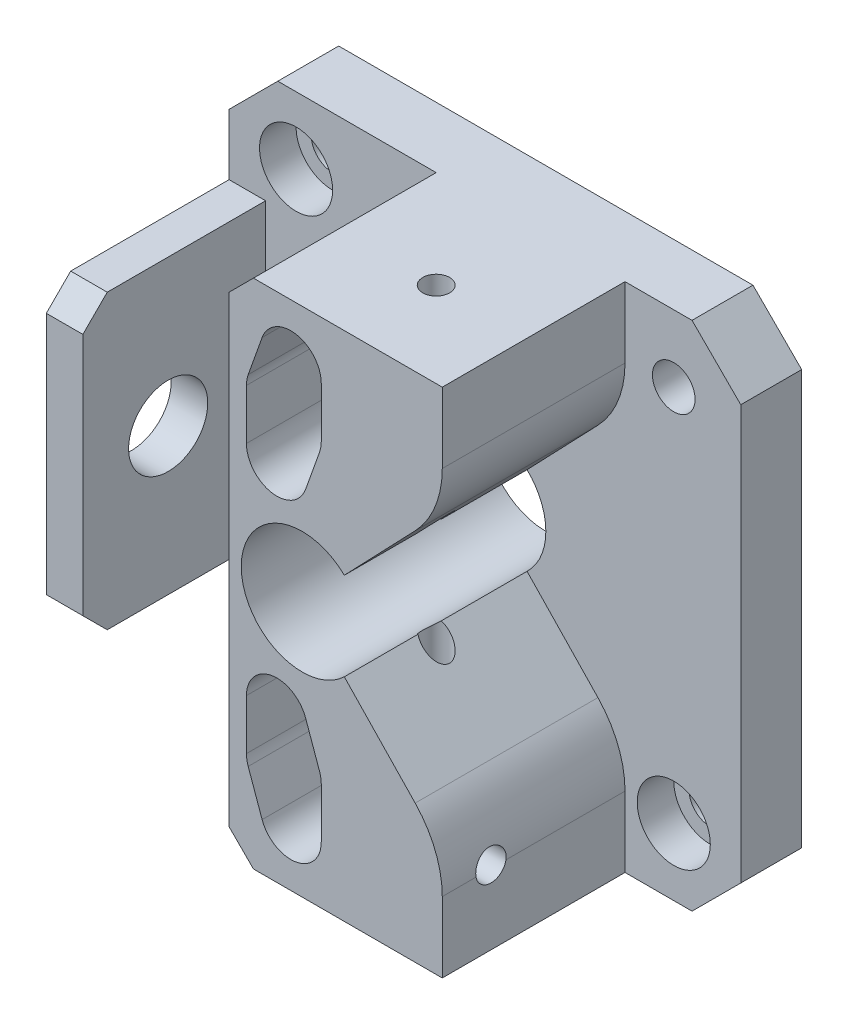
SolidWorks part; units mm, degrees
material "6063-T1"
ref_plane "Piano frontale" through (0, 0, 0) normal (0, 0, 1) x (1, 0, 0)
ref_plane "Piano superiore" through (0, 0, 0) normal (0, 1, 0) x (1, 0, 0)
ref_plane "Piano destro" through (0, 0, 0) normal (1, 0, 0) x (0, 0, -1)
ref_plane "Motor plane" through (0, 0, -25) normal (0, 0, 1) x (1, 0, 0)
sketch "Schizzo1" plane through (0, 0, -25) normal (0, 0, 1) x (1, 0, 0)
  line L1 (15.5, -15.5) -> (-15.5, -15.5) construction
  line L2 (15.5, -15.5) -> (15.5, 15.5) construction
  line L3 (15.5, 15.5) -> (-15.5, 15.5) construction
  line L4 (-15.5, -15.5) -> (-15.5, 15.5) construction
  line L5 (15.5, -15.5) -> (-15.5, 15.5) construction
  line L6 (15.5, 15.5) -> (-15.5, -15.5) construction
  line L7 (21, -21) -> (-21, -21)
  line L8 (21, -21) -> (21, 21)
  line L9 (21, 21) -> (-21, 21)
  line L10 (-21, -21) -> (-21, 21)
  line L11 (21, -21) -> (-21, 21) construction
  line L12 (21, 21) -> (-21, -21) construction
  circle A0 centre (-15.5, 15.5) radius 1.75
  circle A1 centre (15.5, 15.5) radius 1.75
  circle A2 centre (-15.5, -15.5) radius 1.75
  circle A3 centre (15.5, -15.5) radius 1.75
  dimension "D3" = 3.5
  dimension "D1" = 31
  dimension "D2" = 31
  dimension "D5" = 42
  dimension "D6" = 42
extrude "Estrusione-Estrusione1" add sketch "Schizzo1" along normal blind 5
sketch "Schizzo3" plane through (0, 0, -20) normal (0, 0, 1) x (1, 0, 0)
  line L0 (-21, -21) -> (21, -21) construction
  line L1 (11.5, -21) -> (-6, -21)
  line L2 (11.5, -21) -> (11.5, 21)
  line L3 (11.5, 21) -> (-6, 21)
  line L4 (-6, -21) -> (-6, 21)
  line L5 (21, 21) -> (-21, 21) construction
  line L6 (-21, 21) -> (-21, -21) construction
  line L7 (21, -21) -> (21, 21) construction
  dimension "D1" = 15
  dimension "D2" = 9.5
extrude "Estrusione-Estrusione4" add sketch "Schizzo3" along normal blind 15
sketch "Schizzo4" plane through (0, 0, -5) normal (0, 0, 1) x (1, 0, 0)
  circle A0 centre (0, 0) radius 5
  dimension "D1" = 10
extrude "Taglio-Estrusione1" cut sketch "Schizzo4" against normal through all
ref_plane "Piano3" through (4, 0, 0) normal (1, 0, 0) x (0, 0, -1)
sketch "Schizzo6" plane through (0, -21, 0) normal (0, -1, 0) x (1, 0, 0)
  line L0 (11.5, -12) -> (-6, -12) construction
  line L2 (-6, -5) -> (-6, -20) construction
  line L3 (4, -11) -> (4, 11) construction
  line L4 (4, -2.5823) -> (4, -27.3722) construction
  line L9 (23.1, -25) -> (-23.1, -25) construction
  circle A0 centre (4, -12) radius 1.1
  point P10 (4, -12)
  dimension "D1" = 2.2
  dimension "D2" = 13
extrude "Taglio-Estrusione3" cut sketch "Schizzo6" against normal through all
sketch "Schizzo7" plane through (0, 0, -5) normal (0, 0, 1) x (1, 0, 0)
  line L0 (11.5, 0) -> (-6, 0) construction
  line L1 (11.5, -21) -> (11.5, 21) construction
  line L2 (-6, 21) -> (-6, -21) construction
  line L3 (11.5, 12) -> (0, 0)
  line L4 (11.5, 12) -> (11.5, -12)
  line L5 (11.5, -12) -> (0, 0)
  dimension "D1" = 12
extrude "Taglio-Estrusione4" cut sketch "Schizzo7" against normal blind 15
fillet "Raccordo2" radius 8 1 edges at (11.5, 12, -12.5)
fillet "Raccordo3" radius 8 1 edges at (11.5, -12, -12.5)
chamfer "Smusso1" distance 4 angle 45 4 edges at (21, -21, -22.5) (-21, -21, -22.5) (-21, 21, -22.5) (21, 21, -22.5)
sketch "Schizzo22" plane through (11.5, 0, 0) normal (1, 0, 0) x (0, 0, -1)
  point P0 (9, -14.9914)
hole_wizard "Foro filettato M3-2" positions "Schizzo24" profile "Schizzo23" tap size "M3" standard "ISO"
sketch "Schizzo24" plane through (11.5, 0, 0) normal (1, 0, 0) x (0, 0, -1)
  point P0 (9, -14.9914)
sketch "Schizzo23" plane through (11.5, -14.9914, -9) normal (0, 1, 0) x (0, 0, -1)
  line L0 (0, 0) -> (0, 12.7511)
  line L1 (0, 12.7511) -> (1.25, 12)
  line L2 (1.25, 12) -> (1.25, 0)
  line L5 (1.25, 0) -> (0, 0)
  line L10 (0, 12.7511) -> (-1.25, 12) construction
  line L11 (0, -6.35) -> (0, 107.95) construction
  dimension "Tap Drill Dia." = 2.5
  dimension "Tap Drill Depth" = 12
  dimension "Drill Angle" = 118
cosmetic thread "Filettatura del foro2" parameters "D1"=6, "D2"=3
sketch "Schizzo25" plane through (0, 0, -5) normal (0, 0, 1) x (1, 0, 0)
  line L0 (-21, 0) -> (21, 0) construction
  line L1 (-21, 17) -> (-21, -17) construction
  line L2 (21, -17) -> (21, 17) construction
  line L3 (1.5675, 16.296) -> (1.5675, 12.1714)
  line L4 (-3.2878, 17.1342) -> (-4.43, 13.9247)
  line L5 (1.4228, 11.3332) -> (0.2806, 8.1237)
  line L6 (-4.5747, 13.0865) -> (-4.5747, 8.9619)
  line L7 (-4.5747, -13.0865) -> (-4.5747, -8.9619)
  line L8 (1.4228, -11.3332) -> (0.2806, -8.1237)
  line L9 (-3.2878, -17.1342) -> (-4.43, -13.9247)
  line L10 (1.5675, -16.296) -> (1.5675, -12.1714)
  arc A0 (-3.2878, 17.1342) -> (1.5675, 16.296) centre (-0.9325, 16.296) cw
  arc A1 (1.5675, 12.1714) -> (1.4228, 11.3332) centre (-0.9325, 12.1714) cw
  arc A2 (0.2806, 8.1237) -> (-4.5747, 8.9619) centre (-2.0747, 8.9619) cw
  arc A3 (-4.5747, 13.0865) -> (-4.43, 13.9247) centre (-2.0747, 13.0865) cw
  arc A4 (-4.5747, -13.0865) -> (-4.43, -13.9247) centre (-2.0747, -13.0865) ccw
  arc A5 (0.2806, -8.1237) -> (-4.5747, -8.9619) centre (-2.0747, -8.9619) ccw
  arc A6 (1.5675, -12.1714) -> (1.4228, -11.3332) centre (-0.9325, -12.1714) ccw
  arc A7 (-3.2878, -17.1342) -> (1.5675, -16.296) centre (-0.9325, -16.296) ccw
  dimension "D1" = 2.5
extrude "Taglio-Estrusione5" cut sketch "Schizzo25" against normal blind 15
sketch "Schizzo28" plane through (0, 0, -20) normal (0, 0, 1) x (1, 0, 0)
  line L1 (-21, 0) -> (21, 0) construction
  line L2 (-21, 17) -> (-21, -17) construction
  line L3 (21, -17) -> (21, 17) construction
  line L4 (-21, -12) -> (-21, 12)
  line L6 (-21, 12) -> (-18, 12)
  line L7 (-18, 12) -> (-18, -12)
  line L8 (-21, -12) -> (-18, -12)
  point P13 (-18, 0)
  dimension "D1" = 3
  dimension "D2" = 12
extrude "Estrusione-Estrusione5" add sketch "Schizzo28" along normal blind 15
sketch "Schizzo29" plane through (0, 0, -20) normal (0, 0, 1) x (1, 0, 0)
  circle A0 centre (-15.5, 15.5) radius 3
  circle A1 centre (-15.5, -15.5) radius 3
  circle A2 centre (15.5, -15.5) radius 3
  dimension "D1" = 6
extrude "Taglio-Estrusione6" cut sketch "Schizzo29" against normal blind 3
chamfer "Smusso3" distance 2 angle 45 2 edges
sketch "Schizzo30" plane through (-21, 0, 0) normal (-1, 0, 0) x (0, 0, 1)
  line L0 (-5, 0) -> (-25, 0) construction
  line L1 (-5, 12) -> (-5, -12) construction
  line L2 (-25, -23.1) -> (-25, 23.1) construction
  circle A0 centre (-12, 0) radius 3.25
  dimension "D1" = 6.5
  dimension "D2" = 7
extrude "Taglio-Estrusione7" cut sketch "Schizzo30" against normal blind 3
chamfer "Smusso4" distance 2 angle 45 2 edges at (-19.5, -12, -5) (-19.5, 12, -5)
